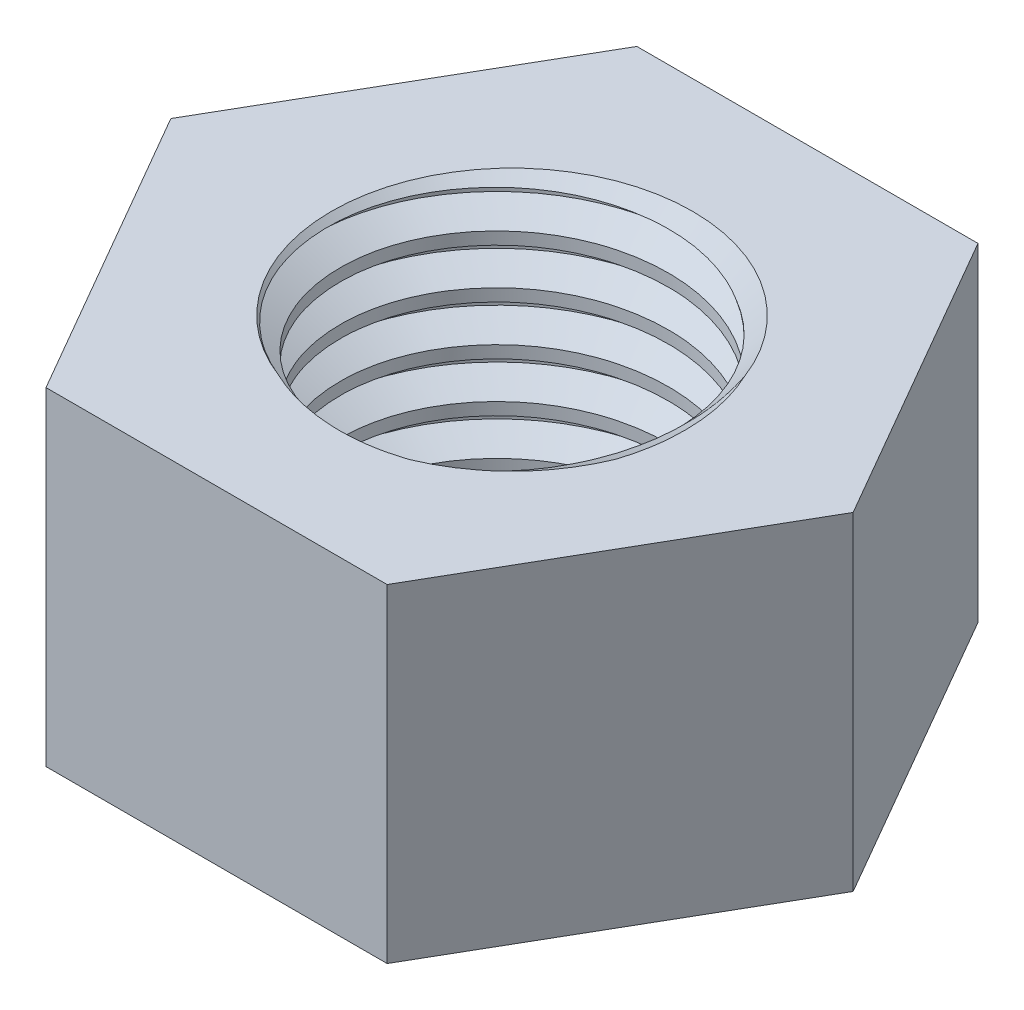
SolidWorks part; units mm, degrees
ref_plane "Front Plane" through (0, 0, 0) normal (0, 0, 1) x (1, 0, 0)
ref_plane "Top Plane" through (0, 0, 0) normal (0, 1, 0) x (1, 0, 0)
ref_plane "Right Plane" through (0, 0, 0) normal (1, 0, 0) x (0, 0, -1)
sketch "Sketch1" plane through (0, 0, 0) normal (0, 1, 0) x (1, 0, 0)
  line L1 (10.3923, 0) -> (5.1962, 9)
  line L2 (5.1962, 9) -> (-5.1962, 9)
  line L3 (-5.1962, 9) -> (-10.3923, 0)
  line L4 (-10.3923, 0) -> (-5.1962, -9)
  line L5 (-5.1962, -9) -> (5.1962, -9)
  line L6 (5.1962, -9) -> (10.3923, 0)
  circle A0 centre (0, 0) radius 9 construction
extrude "Boss-Extrude1" add sketch "Sketch1" along normal blind 10
sketch "Sketch2" plane through (0, 10, 0) normal (0, 1, 0) x (1, 0, 0)
  circle A0 centre (0, 0) radius 5
extrude "Cut-Extrude1" cut sketch "Sketch2" against normal blind 10 contours A0
chamfer "Chamfer1" distance 0.5 angle 45 2 edges at (0, 0, 5) (0, 10, 5)
thread "Thread2" pitch 1.5 method cut profile "Thread Profile3" start angle 0, offset 2, length 0, pitch 1.5, diameter 10
ref_plane "Plane3" through (-5, 11.5, 0) normal (0, 0, 1) x (-1, 0, 0)
sketch "Thread Profile3" plane through (-5, 11.5, 0) normal (0, 0, 1) x (-1, 0, 0)
  line L0 (0, 0) -> (0, 1.5) construction
  line L1 (0, 0) -> (0.8119, 0.4687)
  line L2 (0.8119, 0.4687) -> (0.8119, 0.6562)
  line L3 (0.8119, 0.6562) -> (0, 1.125)
  line L4 (0.8119, 0.5625) -> (0, 0.5625) construction
  line L11 (0, 0) -> (0, 1.125)
  point P2 (0, 0)
  dimension "Pitch" = 1.5
  dimension "Profile_Angle" = 60
  dimension "Profile_Land" = 0.1875
  dimension "Profile_Height" = 0.8119
